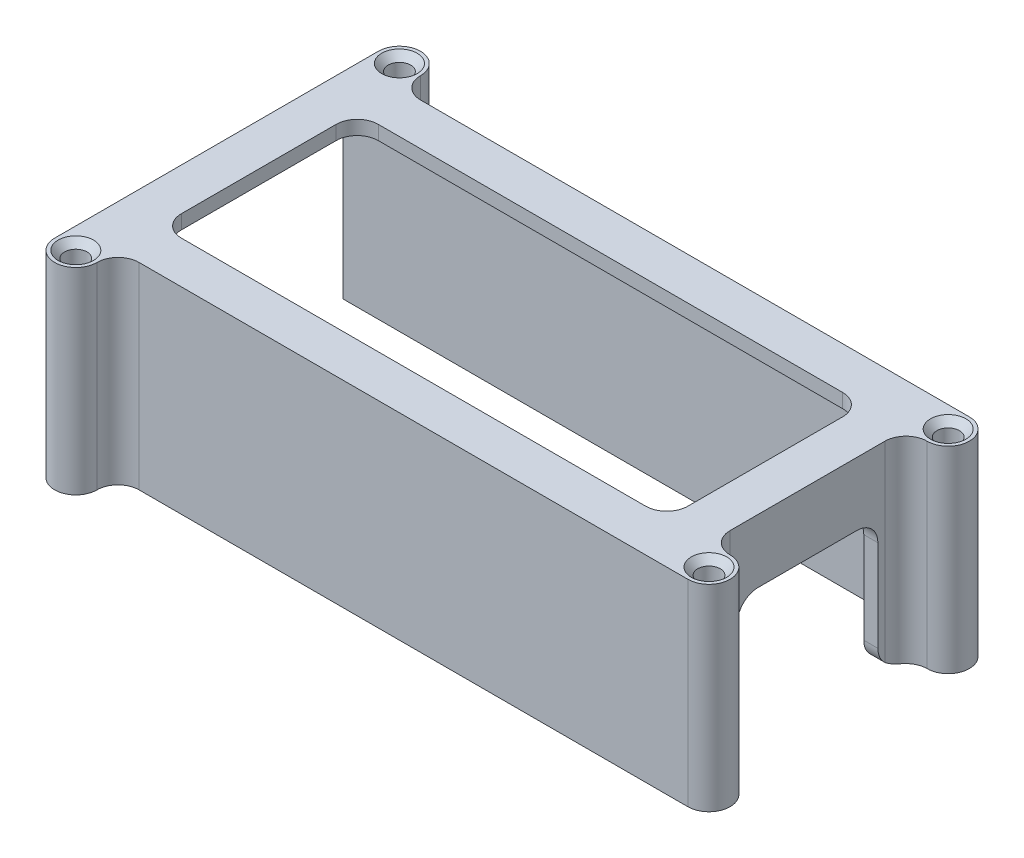
SolidWorks part; units mm, degrees
ref_plane "Front Plane" through (0, 0, 0) normal (0, 0, 1) x (1, 0, 0)
ref_plane "Top Plane" through (0, 0, 0) normal (0, 1, 0) x (1, 0, 0)
ref_plane "Right Plane" through (0, 0, 0) normal (1, 0, 0) x (0, 0, -1)
sketch "Sketch1" plane through (0, 0, 0) normal (0, 1, 0) x (1, 0, 0)
  line L0 (63.5, 28.575) -> (66.675, 31.75) construction
  line L1 (-63.5, -28.575) -> (63.5, -28.575)
  line L2 (-63.5, -28.575) -> (-63.5, 28.575)
  line L3 (-63.5, 28.575) -> (63.5, 28.575)
  line L4 (63.5, -28.575) -> (63.5, 28.575)
  line L5 (-63.5, -28.575) -> (63.5, 28.575) construction
  line L6 (-63.5, 28.575) -> (63.5, -28.575) construction
  line L7 (-66.675, -31.75) -> (66.675, -31.75)
  line L8 (-66.675, -31.75) -> (-66.675, 31.75)
  line L9 (-66.675, 31.75) -> (66.675, 31.75)
  line L10 (66.675, -31.75) -> (66.675, 31.75)
  line L11 (-66.675, -31.75) -> (66.675, 31.75) construction
  line L12 (-66.675, 31.75) -> (66.675, -31.75) construction
  line L13 (63.5, -28.575) -> (66.675, -31.75) construction
  point P0 (0, 0)
  point P6 (0, 0)
  dimension "D1" = 57.15
  dimension "D2" = 127
  dimension "D3" = 3.175
extrude "Boss-Extrude1" add sketch "Sketch1" along normal blind 41.275
sketch "Sketch2" plane through (-66.675, 0, 0) normal (-1, 0, 0) x (0, 0, 1)
  line L0 (-31.75, 0) -> (31.75, 0) construction
  line L1 (-15.875, -30.1625) -> (15.875, -30.1625)
  line L2 (-15.875, -30.1625) -> (-15.875, 30.1625)
  line L3 (-15.875, 30.1625) -> (15.875, 30.1625)
  line L4 (15.875, -30.1625) -> (15.875, 30.1625)
  line L5 (-15.875, -30.1625) -> (15.875, 30.1625) construction
  line L6 (-15.875, 30.1625) -> (15.875, -30.1625) construction
  point P0 (0, 0)
  dimension "D1" = 31.75
  dimension "D2" = 30.1625
extrude "Cut-Extrude1" cut sketch "Sketch2" against normal through all
sketch "Sketch3" plane through (0, 41.275, 0) normal (0, 1, 0) x (1, 0, 0)
  line L0 (-66.675, 31.75) -> (-57.15, 22.225) construction
  line L1 (57.15, -22.225) -> (-57.15, -22.225)
  line L2 (57.15, -22.225) -> (57.15, 22.225)
  line L3 (57.15, 22.225) -> (-57.15, 22.225)
  line L4 (66.675, -31.75) -> (66.675, 31.75)
  line L5 (66.675, 31.75) -> (-66.675, 31.75)
  line L6 (-66.675, 31.75) -> (-66.675, -31.75)
  line L7 (-66.675, -31.75) -> (66.675, -31.75)
  line L8 (66.675, -31.75) -> (66.675, 31.75)
  line L9 (66.675, 31.75) -> (-66.675, 31.75)
  line L10 (-66.675, 31.75) -> (-66.675, -31.75)
  line L11 (-66.675, -31.75) -> (66.675, -31.75)
  line L12 (-57.15, -22.225) -> (-57.15, 22.225)
  line L13 (57.15, -22.225) -> (-57.15, 22.225) construction
  line L14 (57.15, 22.225) -> (-57.15, -22.225) construction
  line L15 (-66.675, -31.75) -> (-57.15, -22.225) construction
  line L16 (63.5, 28.575) -> (-63.5, 28.575) construction
  point P2 (0, 0)
  dimension "D2" = 6.35
  dimension "D1" = 0
extrude "Boss-Extrude2" add sketch "Sketch3" along normal blind 3.175
sketch "Sketch4" plane through (0, 44.45, 0) normal (0, 1, 0) x (1, 0, 0)
  line L0 (66.675, -31.75) -> (66.675, 31.75) construction
  line L1 (71.4375, 31.75) -> (66.675, 31.75)
  line L2 (66.675, 31.75) -> (66.675, 17.4625)
  circle A0 centre (71.4375, 26.9875) radius 1.27 construction
  arc A1 (71.4375, 31.75) -> (71.4375, 22.225) centre (71.4375, 26.9875) cw
  arc A2 (66.675, 17.4625) -> (71.4375, 22.225) centre (71.4375, 17.4625) cw
  dimension "D1" = 4.7625
  dimension "D2" = 2.54
extrude "Boss-Extrude3" add sketch "Sketch4" against normal up to surface (44.45 mm away) up to face at (0, 0, -23.0187)
ref_axis "Axis1" through (71.4375, 0, -26.9875) along (0, 1, 0)
ref_plane "Plane1" through (71.4375, 0, 0) normal (1, 0, 0) x (0, 1, 0)
sketch "Sketch5" plane through (71.4375, 0, 0) normal (1, 0, 0) x (0, 1, 0)
  line L0 (0, -29.5275) -> (42.8625, -29.5275)
  line L1 (42.8625, -29.5275) -> (44.45, -30.9822)
  line L2 (44.45, -31.75) -> (44.45, -22.225) construction
  line L3 (44.45, -30.9822) -> (44.45, -26.9875)
  line L4 (44.45, -26.9875) -> (0, -26.9875) construction
  line L5 (0, -26.9875) -> (44.45, -26.9875) construction
  line L6 (0, -26.9875) -> (0, -29.5275)
  line L7 (0, -22.225) -> (0, -31.75) construction
  line L8 (44.45, -26.9875) -> (0, -26.9875)
  dimension "D1" = 5.08
  dimension "D2" = 42.5
  dimension "D3" = 1.5875
revolve "Cut-Revolve1" cut sketch "Sketch5" angle 360 about L8
sketch "Sketch6" plane through (0, 44.45, 0) normal (0, 1, 0) x (1, 0, 0)
  line L0 (-66.675, 31.75) -> (-66.675, -31.75) construction
  line L1 (-66.675, 36.5125) -> (-66.675, 31.75)
  line L2 (-66.675, 31.75) -> (-52.3875, 31.75)
  line L3 (71.4375, 31.75) -> (-66.675, 31.75) construction
  circle A0 centre (-61.9125, 36.5125) radius 3.9947 construction
  arc A1 (-57.15, 36.5125) -> (-66.675, 36.5125) centre (-61.9125, 36.5125) ccw
  arc A2 (-52.3875, 31.75) -> (-57.15, 36.5125) centre (-52.3875, 36.5125) cw
  arc A3 (71.4375, 22.225) -> (71.4375, 31.75) centre (71.4375, 26.9875) ccw construction
  circle A5 centre (71.4375, 26.9875) radius 3.9947 construction
  arc A6 (-61.9125, 31.75) -> (-57.15, 36.5125) centre (-61.9125, 36.5125) ccw construction
  arc A7 (-66.675, 36.5125) -> (-61.9125, 31.75) centre (-61.9125, 36.5125) ccw construction
  circle A8 centre (-61.9125, 36.5125) radius 2.54
  circle A9 centre (71.4375, 26.9875) radius 2.54 construction
extrude "Boss-Extrude4" add sketch "Sketch6" against normal up to surface (44.45 mm away) up to face at (71.4375, 0, -24.4475)
ref_axis "Axis2" through (-61.9125, 0, -36.5125) along (0, 1, 0)
ref_plane "Plane2" through (-61.9125, 0, 0) normal (-1, 0, 0) x (0, 1, 0)
sketch "Sketch7" plane through (-61.9125, 0, 0) normal (-1, 0, 0) x (0, 1, 0)
  line L0 (42.8625, 39.0525) -> (44.45, 40.5072)
  line L1 (0, 36.5125) -> (44.45, 36.5125) construction
  line L2 (44.45, 36.5125) -> (44.45, 41.275) construction
  line L3 (44.45, 40.5072) -> (44.45, 36.5125)
  line L4 (44.45, 33.9725) -> (44.45, 39.0525) construction
  line L5 (44.45, 36.5125) -> (42.8625, 36.5125)
  line L6 (44.45, 30.9822) -> (42.8625, 29.5275) construction
  line L7 (42.8625, 36.5125) -> (42.8625, 39.0525)
  line L8 (40.0906, 36.5125) -> (42.8625, 39.0525) construction
  line L9 (42.8625, 36.5125) -> (40.0906, 36.5125) construction
  line L10 (44.45, 26.9875) -> (44.45, 30.9822) construction
  line L11 (0, 26.9875) -> (44.45, 26.9875) construction
  line L12 (44.45, 36.5125) -> (44.45, -31.75) construction
revolve "Cut-Revolve2" cut sketch "Sketch7" angle 360 about L9
mirror "Mirror1" about plane through (0, 0, 0) normal (0, 0, 1) of "Cut-Revolve2", "Boss-Extrude4", "Boss-Extrude3", "Cut-Revolve1"
mirror "Mirror2" [suppressed] about plane through (0, 0, 0) normal (1, 0, 0)
sketch "Sketch8" plane through (-63.5, 0, 0) normal (1, 0, 0) x (0, 0, -1)
  line L8 (-15.875, 0) -> (-15.875, 30.1625)
  line L9 (-15.875, 30.1625) -> (15.875, 30.1625)
  line L10 (15.875, 30.1625) -> (15.875, 0)
  line L11 (15.875, 0) -> (28.575, 0)
  line L12 (28.575, 0) -> (28.575, 41.275)
  line L13 (28.575, 41.275) -> (-28.575, 41.275)
  line L14 (-28.575, 41.275) -> (-28.575, 0)
  line L15 (-28.575, 0) -> (-15.875, 0)
  line L16 (-15.875, 0) -> (-15.875, 30.1625)
  line L17 (-15.875, 30.1625) -> (15.875, 30.1625)
  line L18 (15.875, 30.1625) -> (15.875, 0)
  line L19 (15.875, 0) -> (28.575, 0)
  line L20 (28.575, 0) -> (28.575, 41.275)
  line L21 (28.575, 41.275) -> (-28.575, 41.275)
  line L22 (-28.575, 41.275) -> (-28.575, 0)
  line L23 (-28.575, 0) -> (-15.875, 0)
  dimension "D1" = 0
extrude "Cut-Extrude2" cut sketch "Sketch8" against normal through all
fillet "Fillet1" radius 1.5875 5 edges at (63.5, 20.6375, -28.575) (-1.5875, 41.275, -28.575) (63.5, 20.6375, 28.575) (63.5, 41.275, 0) (-1.5875, 41.275, 28.575)
fillet "Fillet2" radius 4.7625 8 edges at (65.0875, 0, 15.875) (65.0875, 0, -15.875) (65.0875, 30.1625, -15.875) (65.0875, 30.1625, 15.875) (-57.15, 42.8625, 22.225) (-57.15, 42.8625, -22.225) (57.15, 42.8625, 22.225) (57.15, 42.8625, -22.225)
